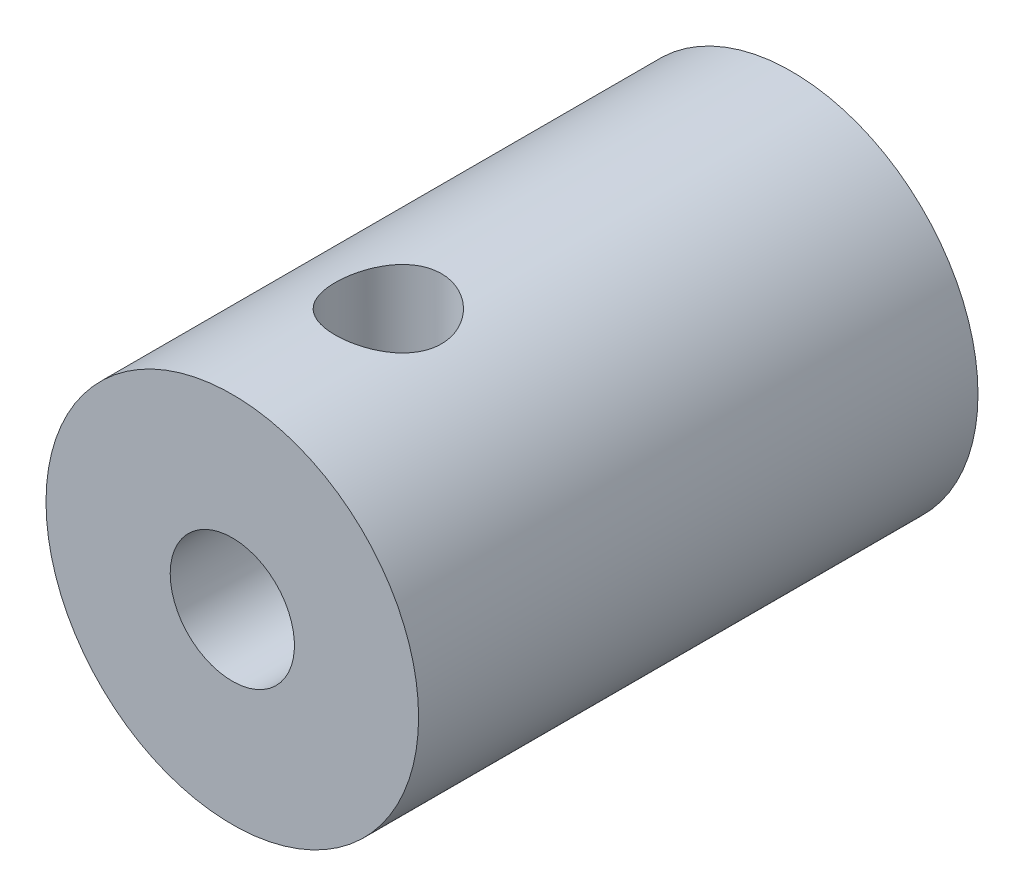
SolidWorks part; units mm, degrees
ref_plane "Front Plane" through (0, 0, 0) normal (0, 0, 1) x (1, 0, 0)
ref_plane "Top Plane" through (0, 0, 0) normal (0, 1, 0) x (1, 0, 0)
ref_plane "Right Plane" through (0, 0, 0) normal (1, 0, 0) x (0, 0, -1)
sketch "Sketch1" plane through (0, 0, 0) normal (0, 0, 1) x (1, 0, 0)
  circle A0 centre (0, 0) radius 4.7625
  dimension "D1" = 9.525
extrude "Boss-Extrude1" add sketch "Sketch1" along normal blind 14.3002
sketch "Sketch2" plane through (0, 0, 0) normal (0, 0, -1) x (-1, 0, 0)
  circle A0 centre (0, 0) radius 1.5875
  circle A1 centre (0, 0) radius 4.7625
  circle A2 centre (0, 0) radius 4.7625
  circle A3 centre (0, 0) radius 3.175
  dimension "D2" = 3.175
  dimension "D3" = 6.35
  dimension "D1" = 0
extrude "Cut-Extrude1" cut sketch "Sketch2" against normal through all contours A0 region at (0, 0, 0)
extrude "Cut-Extrude2" cut sketch "Sketch2<3>" against normal blind 6.35 contours A3 A0 region at (3.0852, 0, 0)
sketch "Sketch2<3>" plane through (0, 0, 0) normal (0, 0, -1) x (-1, 0, 0) same geometry as "Sketch2"
sketch "Sketch3" plane through (0, 0, 14.3002) normal (0, 0, 1) x (1, 0, 0)
  line L0 (0, 0) -> (0, 4.7625) construction
  circle A0 centre (0, 0) radius 4.7625 construction
ref_plane "Plane1" through (0, 4.7625, 0) normal (0, 1, 0) x (1, 0, 0)
sketch "Sketch4" plane through (0, 4.7625, 0) normal (0, 1, 0) x (1, 0, 0)
  line L0 (-4.7625, -14.3002) -> (4.7625, -14.3002) construction
  line L1 (4.7625, -14.3002) -> (4.7625, 0) construction
  line L3 (-4.7625, 0) -> (-4.7625, -14.3002) construction
  line L4 (-4.7625, -14.3002) -> (4.7625, -14.3002)
  line L5 (4.7625, -14.3002) -> (4.7625, 0)
  line L6 (0, -14.3002) -> (0, 49985.6998) construction
  line L7 (-4.7625, 0) -> (-4.7625, -14.3002)
  line L9 (3.175, -6.35) -> (-3.175, -6.35) construction
  line L10 (3.175, -6.35) -> (-3.175, -6.35)
  line L11 (4.7625, 0) -> (-4.7625, 0) construction
  circle A0 centre (0, -10.3124) radius 1.3589
  point P5 (0, -14.3002)
  dimension "D1" = 2.7178
  dimension "D2" = 10.3124
extrude "Cut-Extrude3" cut sketch "Sketch4" against normal through all contours L6 L10 A0 | L10 L6 A0 region at (0, 4.7625, 10.3124)
